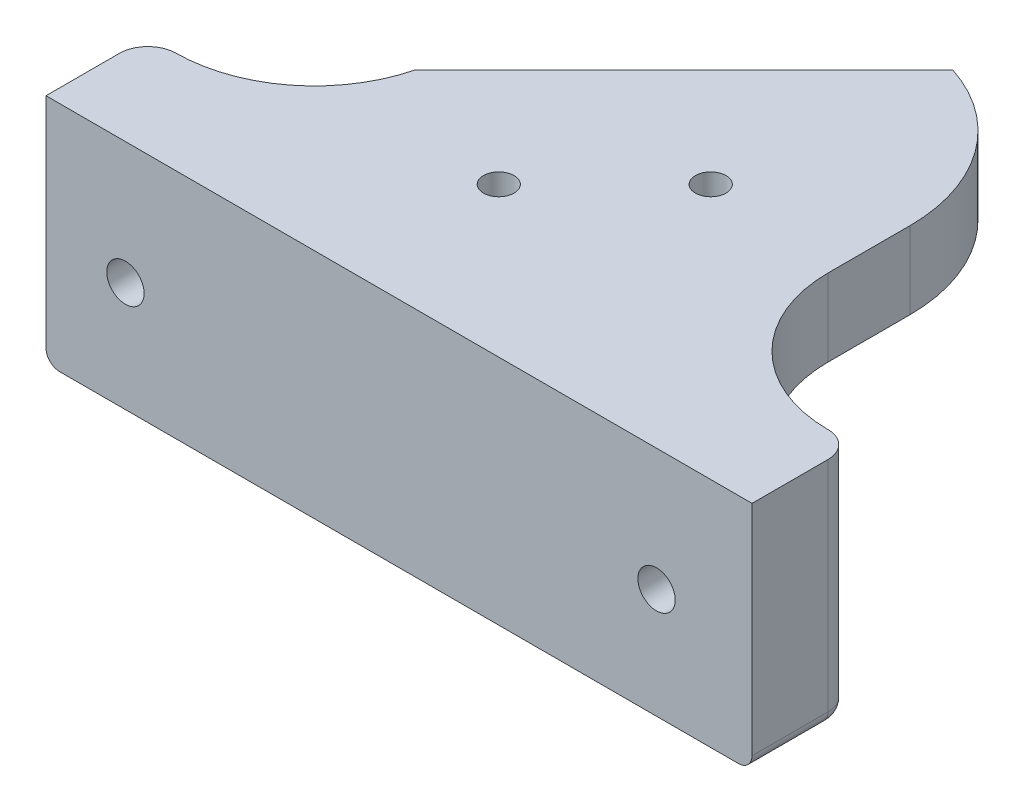
SolidWorks part; units mm, degrees
ref_plane "Front Plane" through (0, 0, 0) normal (0, 0, 1) x (1, 0, 0)
ref_plane "Top Plane" through (0, 0, 0) normal (0, 1, 0) x (1, 0, 0)
ref_plane "Right Plane" through (0, 0, 0) normal (1, 0, 0) x (0, 0, -1)
sketch "Sketch1" plane through (0, 0, 0) normal (0, 0, 1) x (1, 0, 0)
  line L5 (-69.4768, -14.6899) -> (34.4916, -14.6899)
  line L6 (-69.4768, -14.6899) -> (-69.4768, 19.4962)
  line L7 (-69.4768, 19.4962) -> (34.4916, 19.4962)
  line L8 (34.4916, -14.6899) -> (34.4916, 19.4962)
extrude "Boss-Extrude1" add sketch "Sketch1" along normal blind 15
sketch "Sketch2" plane through (0, 0, 0) normal (0, 0, -1) x (-1, 0, 0)
  line L0 (69.4768, 19.4962) -> (69.4768, -14.6899) construction
  line L1 (69.4768, 8.1286) -> (-34.4916, 8.1286)
  line L2 (69.4768, 8.1286) -> (69.4768, 19.4962)
  line L3 (69.4768, 19.4962) -> (-34.4916, 19.4962)
  line L4 (-34.4916, 8.1286) -> (-34.4916, 19.4962)
  line L5 (-34.4916, 19.4962) -> (69.4768, 19.4962) construction
  line L6 (-34.4916, -14.6899) -> (-34.4916, 19.4962) construction
extrude "Boss-Extrude2" add sketch "Sketch2" along normal blind 60
sketch "Sketch3" plane through (0, 8.1286, 0) normal (0, -1, 0) x (1, 0, 0)
  line L0 (-45.5992, 0) -> (-45.5992, -15.4)
  line L1 (-69.4768, 0) -> (34.4916, 0) construction
  line L2 (-45.5992, 0) -> (-45.5992, -15.4) construction
  line L3 (-45.5992, -15.4) -> (-5.9598, -55.0394)
  line L7 (34.4916, 15) -> (34.4916, 0) construction
  line L8 (34.4916, -60) -> (34.4916, 0) construction
  line L9 (34.4916, 0) -> (34.4916, -60)
  line L10 (34.4916, -60) -> (-69.4768, -60) construction
  line L11 (34.4916, -60) -> (-69.4768, -60)
  line L12 (-69.4768, -60) -> (-69.4768, 0)
  line L13 (-69.4768, 0) -> (-45.5992, 0)
  line L20 (34.4916, 0) -> (10.7044, 0)
  line L21 (10.7044, 0) -> (10.7044, -55.0394)
  line L22 (10.7044, -55.0394) -> (-5.9598, -55.0394)
  line L23 (-45.5992, -15.4) -> (-5.5992, -55.4) construction
  line L24 (-11.6167, -60.6962) -> (-5.9598, -55.0394) construction
  point P19 (-4.9092, -53.7224)
  point P24 (-5.8019, -55.0394)
extrude "Cut-Extrude1" cut sketch "Sketch3" against normal through all
hole_wizard "M4 Clearance Hole1" positions "3DSketch2" profile "Sketch4" hole size "M4" standard "ISO" end condition through all
sketch3d "3DSketch2"
  point P0 (-9.2371, 8.1286, -22.6408)
  point P2 (-24.8421, 8.1286, -7.0358)
sketch "Sketch4" plane through (-9.2371, 8.1286, -22.6408) normal (1, 0, 0) x (0, 0, -1)
  line L0 (0, 0) -> (0, 11.3676)
  line L1 (0, 11.3676) -> (2.25, 11.3676)
  line L2 (2.25, 11.3676) -> (2.25, 0)
  line L5 (2.25, 0) -> (0, 0)
  line L11 (0, -6.35) -> (0, 107.95) construction
  dimension "Thru Hole Dia." = 4.5
  dimension "Thru Hole Depth" = 11.3676
hole_wizard "M5 Clearance Hole1" positions "3DSketch3" profile "Sketch5" hole size "M5" standard "ISO" end condition through all
sketch3d "3DSketch3"
  point P0 (-57.7823, 1.4985, 0)
  point P2 (20.4265, 1.4985, 0)
sketch "Sketch5" plane through (-57.7823, 1.4985, 0) normal (1, 0, 0) x (0, 1, 0)
  line L0 (0, 0) -> (0, 15)
  line L1 (0, 15) -> (2.75, 15)
  line L2 (2.75, 15) -> (2.75, 0)
  line L5 (2.75, 0) -> (0, 0)
  line L11 (0, -6.35) -> (0, 107.95) construction
  dimension "Thru Hole Dia." = 5.5
  dimension "Thru Hole Depth" = 15
fillet "Fillet1" radius 20 1 edges at (10.7044, 13.8124, 0)
fillet "Fillet2" radius 20.5 1 edges at (-45.5992, 13.8124, 0)
fillet "Fillet4" radius 4.2 1 edges at (-69.4768, 2.4032, 0)
fillet "Fillet8" radius 3.8 1 edges at (34.4916, 2.4032, 0)
fillet "Fillet9" radius 24.2 1 edges at (10.7044, 13.8124, -55.0394)
fillet "Fillet10" radius 2 5 edges at (-69.4768, -14.6899, 9.6) (-68.2466, -14.6899, 1.2302) (34.4916, -14.6899, 9.4) (33.3786, -14.6899, 1.113) (-17.2926, -14.6899, 0)
